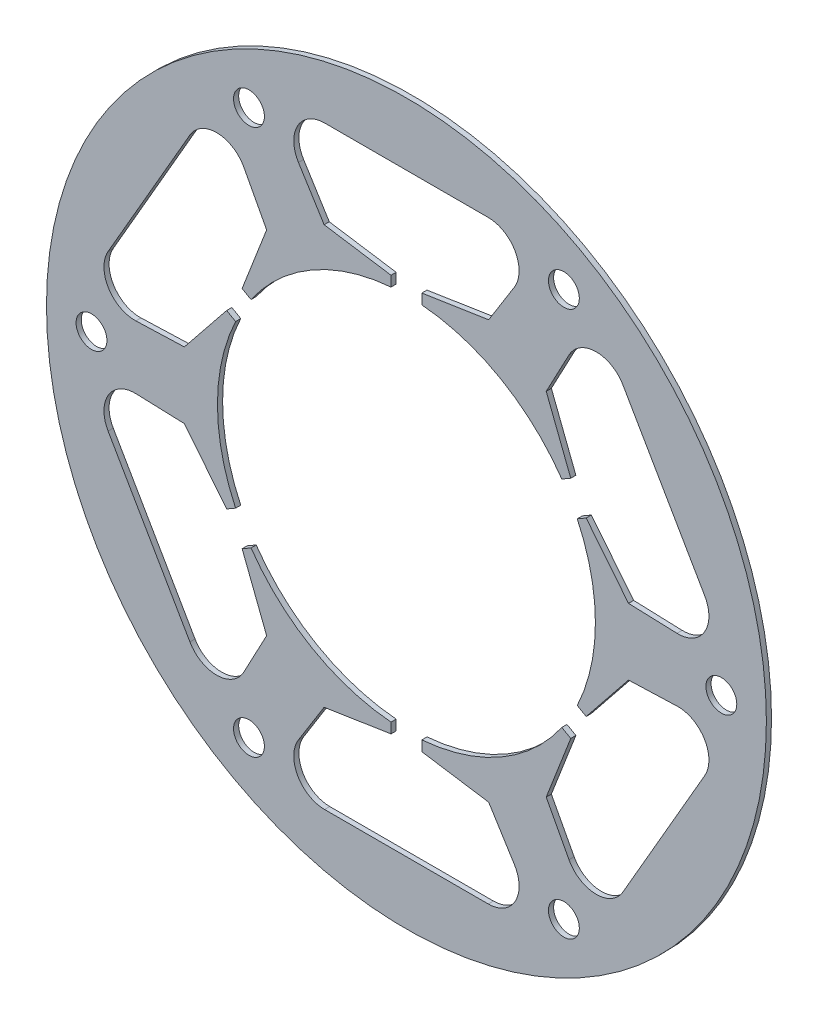
SolidWorks part; units mm, degrees
ref_plane "Ön Düzlem" through (0, 0, 0) normal (0, 0, 1) x (1, 0, 0)
ref_plane "Üst Düzlem" through (0, 0, 0) normal (0, 1, 0) x (1, 0, 0)
ref_plane "Sağ Düzlem" through (0, 0, 0) normal (1, 0, 0) x (0, 0, -1)
sketch "Çizim1" plane through (0, 0, 0) normal (0, 0, 1) x (1, 0, 0)
  line L0 (-1.5, 18.3137) -> (-1.5, 19.3137)
  line L1 (1.5, 18.3137) -> (1.5, 19.3137)
  line L2 (1.5, 19.3137) -> (8, 20.3137)
  line L3 (-1.5, 19.3137) -> (-8, 20.3137)
  line L4 (8, 20.3137) -> (10.5, 24.3137)
  line L5 (-8, 20.3137) -> (-10.5, 24.3137)
  line L6 (-7.956, 28.9037) -> (7.956, 28.9037)
  line L7 (13.5922, 17.085) -> (15.8063, 21.2501)
  line L8 (15.9761, 10.9559) -> (13.5922, 17.085)
  line L9 (15.1101, 10.4559) -> (15.9761, 10.9559)
  line L10 (16.6101, 7.8578) -> (17.4761, 8.3578)
  line L11 (17.4761, 8.3578) -> (21.5922, 3.2286)
  line L12 (21.5922, 3.2286) -> (26.3063, 3.0636)
  line L13 (21.0533, 21.3419) -> (29.0093, 7.5617)
  line L14 (21.5922, -3.2286) -> (26.3063, -3.0636)
  line L15 (17.4761, -8.3578) -> (21.5922, -3.2286)
  line L16 (16.6101, -7.8578) -> (17.4761, -8.3578)
  line L17 (15.1101, -10.4559) -> (15.9761, -10.9559)
  line L18 (15.9761, -10.9559) -> (13.5922, -17.085)
  line L19 (13.5922, -17.085) -> (15.8063, -21.2501)
  line L20 (29.0093, -7.5617) -> (21.0533, -21.3419)
  line L21 (8, -20.3137) -> (10.5, -24.3137)
  line L22 (1.5, -19.3137) -> (8, -20.3137)
  line L23 (1.5, -18.3137) -> (1.5, -19.3137)
  line L24 (-1.5, -18.3137) -> (-1.5, -19.3137)
  line L25 (-1.5, -19.3137) -> (-8, -20.3137)
  line L26 (-8, -20.3137) -> (-10.5, -24.3137)
  line L27 (7.956, -28.9037) -> (-7.956, -28.9037)
  line L28 (-13.5922, -17.085) -> (-15.8063, -21.2501)
  line L29 (-15.9761, -10.9559) -> (-13.5922, -17.085)
  line L30 (-15.1101, -10.4559) -> (-15.9761, -10.9559)
  line L31 (-16.6101, -7.8578) -> (-17.4761, -8.3578)
  line L32 (-17.4761, -8.3578) -> (-21.5922, -3.2286)
  line L33 (-21.5922, -3.2286) -> (-26.3063, -3.0636)
  line L34 (-21.0533, -21.3419) -> (-29.0093, -7.5617)
  line L35 (-21.5922, 3.2286) -> (-26.3063, 3.0636)
  line L36 (-17.4761, 8.3578) -> (-21.5922, 3.2286)
  line L37 (-16.6101, 7.8578) -> (-17.4761, 8.3578)
  line L38 (-15.1101, 10.4559) -> (-15.9761, 10.9559)
  line L39 (-15.9761, 10.9559) -> (-13.5922, 17.085)
  line L40 (-13.5922, 17.085) -> (-15.8063, 21.2501)
  line L41 (-29.0093, 7.5617) -> (-21.0533, 21.3419)
  circle A0 centre (0, 0) radius 35
  arc A1 (-16.6101, 7.8578) -> (-16.6101, -7.8578) centre (0, 0) ccw
  arc A2 (-7.956, 28.9037) -> (-10.5, 24.3137) centre (-7.956, 25.9037) ccw
  arc A3 (10.5, 24.3137) -> (7.956, 28.9037) centre (7.956, 25.9037) ccw
  arc A4 (26.3063, 3.0636) -> (29.0093, 7.5617) centre (26.4112, 6.0617) ccw
  arc A5 (21.0533, 21.3419) -> (15.8063, 21.2501) centre (18.4552, 19.8419) ccw
  arc A6 (15.8063, -21.2501) -> (21.0533, -21.3419) centre (18.4552, -19.8419) ccw
  arc A7 (29.0093, -7.5617) -> (26.3063, -3.0636) centre (26.4112, -6.0617) ccw
  arc A8 (-10.5, -24.3137) -> (-7.956, -28.9037) centre (-7.956, -25.9037) ccw
  arc A9 (7.956, -28.9037) -> (10.5, -24.3137) centre (7.956, -25.9037) ccw
  arc A10 (-26.3063, -3.0636) -> (-29.0093, -7.5617) centre (-26.4112, -6.0617) ccw
  arc A11 (-21.0533, -21.3419) -> (-15.8063, -21.2501) centre (-18.4552, -19.8419) ccw
  arc A12 (-15.8063, 21.2501) -> (-21.0533, 21.3419) centre (-18.4552, 19.8419) ccw
  arc A13 (-29.0093, 7.5617) -> (-26.3063, 3.0636) centre (-26.4112, 6.0617) ccw
  arc A14 (-15.1101, -10.4559) -> (-1.5, -18.3137) centre (0, 0) ccw
  arc A15 (1.5, -18.3137) -> (15.1101, -10.4559) centre (0, 0) ccw
  arc A16 (16.6101, -7.8578) -> (16.6101, 7.8578) centre (0, 0) ccw
  arc A17 (15.1101, 10.4559) -> (1.5, 18.3137) centre (0, 0) ccw
  arc A18 (-1.5, 18.3137) -> (-15.1101, 10.4559) centre (0, 0) ccw
  circle A19 centre (-15.3101, 26.5179) radius 4.3797 construction
  circle A20 centre (-15.3101, 26.5179) radius 1.5
  circle A21 centre (15.3101, 26.5179) radius 1.5
  circle A22 centre (30.6203, 0) radius 1.5
  circle A23 centre (15.3101, -26.5179) radius 1.5
  circle A24 centre (-15.3101, -26.5179) radius 1.5
  circle A25 centre (-30.6203, 0) radius 1.5
  point P79 (0, 0)
  point P80 (0, 0)
  point P81 (0, 0)
  point P93 (0, 0)
  dimension "D1" = 70
  dimension "D2" = 36.75
  dimension "D15" = 6
  dimension "D16" = 6
  dimension "D18" = 3
  dimension "D3" = 3
  dimension "D4" = 1.5
  dimension "D5" = 1
  dimension "D6" = 1
  dimension "D7" = 1
  dimension "D8" = 1
  dimension "D9" = 16
  dimension "D10" = 8
  dimension "D11" = 4
  dimension "D12" = 4
  dimension "D13" = 21
  dimension "D14" = 10.5
  dimension "D17" = 6
  dimension "D19" = 6
extrude "Yükseklik-Ekstrüzyon1" add sketch "Çizim1" along normal blind 0.5
